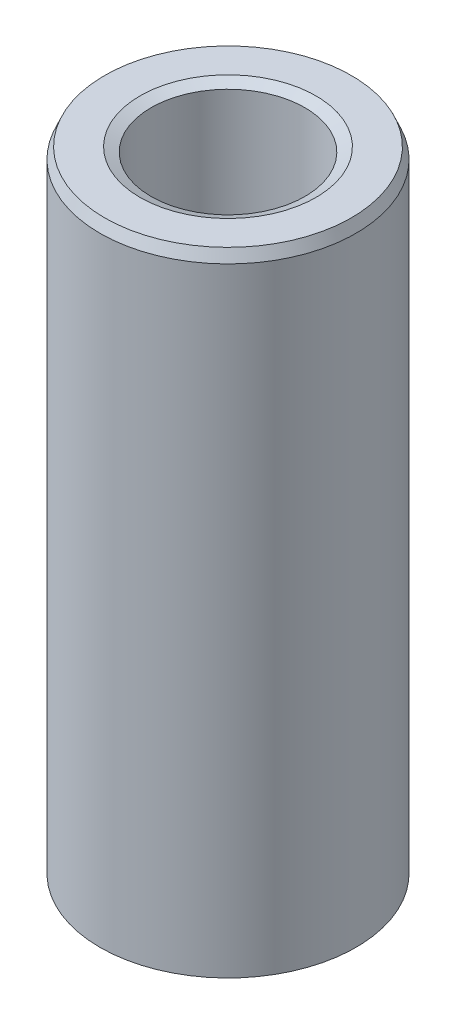
SolidWorks part; units mm, degrees
ref_plane "Front Plane" through (0, 0, 0) normal (0, 0, 1) x (1, 0, 0)
ref_plane "Top Plane" through (0, 0, 0) normal (0, 1, 0) x (1, 0, 0)
ref_plane "Right Plane" through (0, 0, 0) normal (1, 0, 0) x (0, 0, -1)
sketch "Sketch1" plane through (0, 0, 0) normal (0, 1, 0) x (1, 0, 0)
  circle A0 centre (0, 0) radius 37.5
  dimension "SLEEVE_OD" = 75
extrude "Boss-Extrude1" add sketch "Sketch1" along normal blind 185.7281
sketch "Sketch2" plane through (0, 0, 0) normal (0, 1, 0) x (1, 0, 0)
  circle A0 centre (0, 0) radius 22.5436
  dimension "BORE_D" = 45.0873
extrude "Cut-Extrude1" cut sketch "Sketch2" along normal through all
chamfer "Chamfer1" distance 3.2328 angle 23.014 4 edges at (0, 185.7281, 22.5436) (0, 0, 22.5436) (0, 0, 37.5) (0, 185.7281, 37.5) first distance on face at (0, 185.7281, 22.5436) first distance on face at (0, 0, 22.5436) first distance on face at (0, 185.7281, 37.5)
